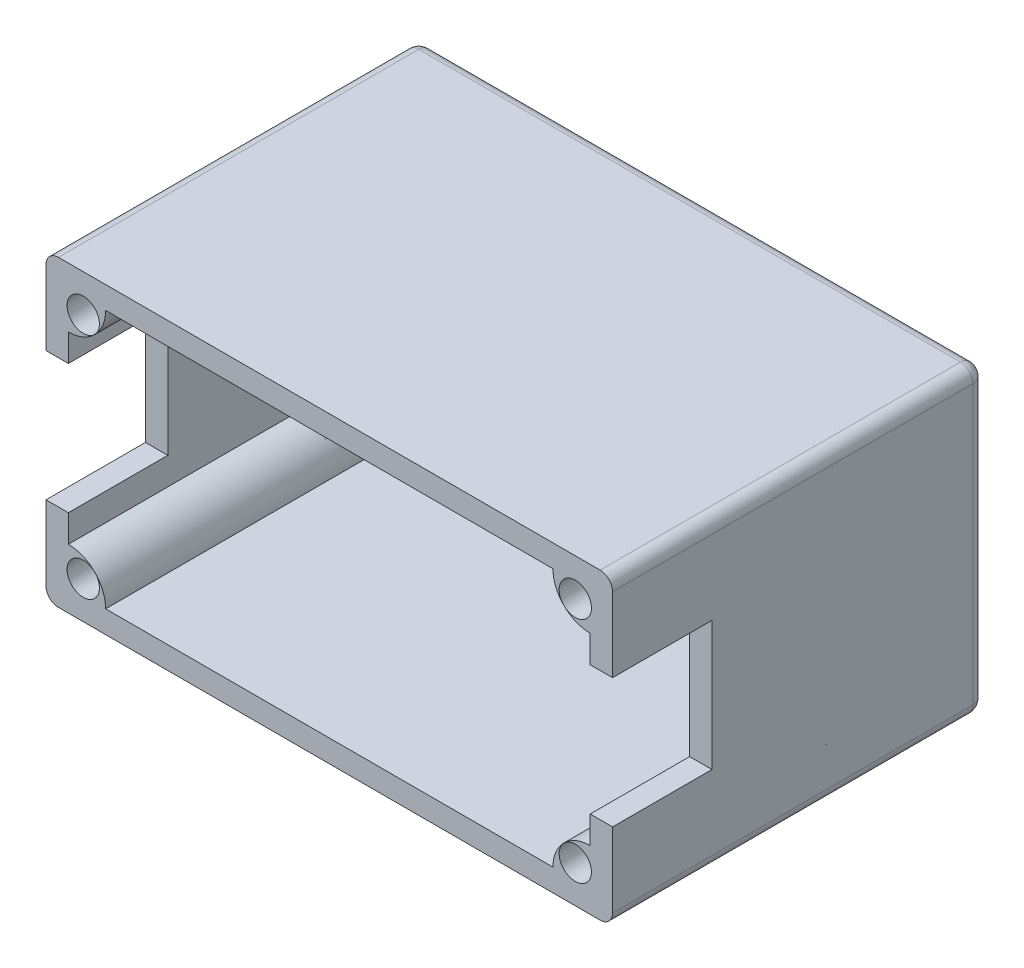
SolidWorks part; units mm, degrees
ref_plane "前视基准面" through (0, 0, 0) normal (0, 0, 1) x (1, 0, 0)
ref_plane "上视基准面" through (0, 0, 0) normal (0, 1, 0) x (1, 0, 0)
ref_plane "右视基准面" through (0, 0, 0) normal (1, 0, 0) x (0, 0, -1)
sketch "草图1" plane through (0, 0, 0) normal (0, 0, 1) x (1, 0, 0)
  line L1 (-11.4, 6.1) -> (11.4, 6.1)
  line L2 (-11.4, 6.1) -> (-11.4, -6.1)
  line L3 (-11.4, -6.1) -> (11.4, -6.1)
  line L4 (11.4, 6.1) -> (11.4, -6.1)
  line L5 (-11.4, 6.1) -> (11.4, -6.1) construction
  line L6 (-11.4, -6.1) -> (11.4, 6.1) construction
  point P0 (0, 0)
  dimension "D1" = 22.8
  dimension "D2" = 12.2
extrude "凸台-拉伸1" add sketch "草图1" along normal blind 15
sketch "草图2" plane through (0, 0, 15) normal (0, 0, 1) x (1, 0, 0)
  line L0 (11.4, 6.1) -> (-11.4, 6.1) construction
  line L1 (-10.5, 5.2) -> (10.5, 5.2)
  line L2 (-10.5, 5.2) -> (-10.5, -5.2)
  line L3 (-10.5, -5.2) -> (10.5, -5.2)
  line L4 (10.5, 5.2) -> (10.5, -5.2)
  line L5 (-11.4, 6.1) -> (-11.4, -6.1) construction
  line L6 (-11.4, -6.1) -> (11.4, -6.1) construction
  line L7 (11.4, -6.1) -> (11.4, 6.1) construction
  dimension "D1" = 0.9
  dimension "D2" = 0.9
  dimension "D3" = 0.9
  dimension "D4" = 0.9
extrude "切除-拉伸1" cut sketch "草图2" against normal blind 13
sketch "草图3" plane through (0, 0, 2) normal (0, 0, 1) x (1, 0, 0)
  line L0 (10.5, -5.2) -> (10.5, 5.2) construction
  line L1 (10.5, 5.2) -> (-10.5, 5.2) construction
  line L2 (10.5, -5.2) -> (10.5, 5.2) construction
  line L3 (-10.5, -5.2) -> (10.5, -5.2) construction
  line L4 (-10.5, 5.2) -> (-10.5, -5.2) construction
  circle A0 centre (9.9, 4.6) radius 0.65
  circle A1 centre (-9.9, -4.6) radius 0.65
  circle A2 centre (9.9, -4.6) radius 0.65
  circle A3 centre (-9.9, 4.6) radius 0.65
  dimension "D1" = 1.3
  dimension "D5" = 1.3
  dimension "D7" = 1.3
  dimension "D10" = 0.6
  dimension "D11" = 1.3
  dimension "D2" = 0.6
  dimension "D3" = 0.6
  dimension "D4" = 19.8
  dimension "D6" = 0.6
  dimension "D8" = 0.6
  dimension "D9" = 0.6
  dimension "D12" = 0.6
sketch "草图4" plane through (0, 0, 15) normal (0, 0, 1) x (1, 0, 0)
  line L0 (-11.4, 6.1) -> (-11.4, -6.1) construction
  line L1 (-11.4, 2.6) -> (-10.5, 2.6)
  line L2 (-11.4, 2.6) -> (-11.4, -2.6)
  line L3 (-11.4, -2.6) -> (-10.5, -2.6)
  line L4 (-10.5, 2.6) -> (-10.5, -2.6)
  line L5 (-10.5, 5.2) -> (-10.5, -5.2) construction
  line L6 (11.4, 6.1) -> (-11.4, 6.1) construction
  line L8 (-11.4, -6.1) -> (11.4, -6.1) construction
  dimension "D1" = 3.5
  dimension "D2" = 3.5
extrude "切除-拉伸2" cut sketch "草图4" against normal blind 4
fillet "圆角1" radius 0.5 4 edges at (0, 6.1, 0) (-11.4, 0, 0) (0, -6.1, 0) (11.4, 0, 0)
sketch "草图7" plane through (0, 0, 2) normal (0, 0, 1) x (1, 0, 0)
  line L0 (-5.85, -2.45) -> (5.15, -2.45) construction
  line L1 (-5.85, -0.2) -> (5.15, -0.2)
  line L2 (-5.85, -4.7) -> (5.15, -4.7)
  line L3 (-10.5, -5.2) -> (10.5, -5.2) construction
  line L5 (10.5, -5.2) -> (10.5, 5.2) construction
  arc A0 (-5.85, -0.2) -> (-5.85, -4.7) centre (-5.85, -2.45) ccw
  arc A1 (5.15, -4.7) -> (5.15, -0.2) centre (5.15, -2.45) ccw
  point P2 (-0.35, -2.45)
  point P7 (-8.1, -2.45)
  point P8 (7.4, -2.45)
  dimension "D2" = 15.5
  dimension "D1" = 11
  dimension "D3" = 0.5
  dimension "D4" = 10.85
extrude "切除-拉伸5" cut sketch "草图7" against normal blind 2
fillet "圆角2" radius 0.5 8 edges at (11.2536, 5.9536, 0.1464) (11.2536, -5.9536, 0.1464) (-11.2536, -5.9536, 0.1464) (-11.2536, 5.9536, 0.1464) (11.4, 6.1, 7.75) (11.4, -6.1, 7.75) (-11.4, -6.1, 7.75) (-11.4, 6.1, 7.75)
sketch "草图8" plane through (0, 0, 15) normal (0, 0, 1) x (1, 0, 0)
  line L0 (10.5, -5.2) -> (10.5, 5.2) construction
  line L1 (10.5, 2.6) -> (11.4, 2.6)
  line L2 (10.5, 2.6) -> (10.5, -2.6)
  line L3 (10.5, -2.6) -> (11.4, -2.6)
  line L4 (11.4, 2.6) -> (11.4, -2.6)
  line L5 (11.4, -5.6) -> (11.4, 5.6) construction
  line L6 (10.9, 6.1) -> (-10.9, 6.1) construction
  line L7 (-10.9, -6.1) -> (10.9, -6.1) construction
  dimension "D1" = 3.5
  dimension "D2" = 3.5
extrude "切除-拉伸6" cut sketch "草图8" against normal blind 4
sketch "草图10" plane through (0, 0, 2) normal (0, 0, 1) x (1, 0, 0)
  line L0 (-10.5, -2.6) -> (-10.5, -5.2) construction
  line L1 (-10.5, -5.2) -> (10.5, -5.2) construction
  line L2 (-10.5, 5.2) -> (-10.5, -5.2) construction
  line L3 (-10.5, -5.2) -> (10.5, -5.2) construction
  line L4 (10.5, 5.2) -> (-10.5, 5.2) construction
  line L5 (10.5, -5.2) -> (10.5, 5.2) construction
  line L6 (10.5, -5.2) -> (10.5, -2.6) construction
  line L7 (10.5, 5.2) -> (-10.5, 5.2) construction
  line L8 (-10.5, 5.2) -> (-10.5, 2.6) construction
  line L9 (-10.5, 3.7) -> (-10.5, 5.2)
  line L10 (10.5, 2.6) -> (10.5, 5.2) construction
  line L11 (9, 5.2) -> (10.5, 5.2)
  line L12 (10.5, 5.2) -> (10.5, 3.7)
  line L13 (-10.5, 5.2) -> (-9, 5.2)
  line L14 (10.5, -3.7) -> (10.5, -5.2)
  line L15 (10.5, -5.2) -> (9, -5.2)
  line L16 (-10.5, -3.7) -> (-10.5, -5.2)
  line L17 (-10.5, -5.2) -> (-9, -5.2)
  arc A0 (-10.5, -3.7) -> (-9, -5.2) centre (-10.5, -5.2) cw
  arc A1 (10.5, -3.7) -> (9, -5.2) centre (10.5, -5.2) ccw
  arc A2 (-9, 5.2) -> (-10.5, 3.7) centre (-10.5, 5.2) cw
  arc A3 (9, 5.2) -> (10.5, 3.7) centre (10.5, 5.2) ccw
  dimension "D3" = 1.5
  dimension "D6" = 1.5
  dimension "D7" = 1.5
  dimension "D9" = 1.5
  dimension "D10" = 1.5
  dimension "D12" = 1.5
  dimension "D1" = 1.5
  dimension "D2" = 1.5
  dimension "D4" = 1.5
  dimension "D5" = 1.5
  dimension "D8" = 1.5
  dimension "D11" = 1.5
extrude "凸台-拉伸2" add sketch "草图10" along normal blind 13
extrude "切除-拉伸8" cut sketch "草图3" along normal through all and the other way through all
sketch "草图9" plane through (0, 0, 0) normal (0, 0, -1) x (-1, 0, 0)
  circle A0 centre (-9.9, 4.6) radius 1.1
  circle A1 centre (9.9, 4.6) radius 1.1
  circle A2 centre (9.9, -4.6) radius 1.1
  circle A3 centre (-9.9, -4.6) radius 1.1
  dimension "D1" = 2.2
  dimension "D2" = 2.2
  dimension "D3" = 2.2
  dimension "D4" = 2.2
extrude "切除-拉伸9" cut sketch "草图9" against normal blind 0.5
